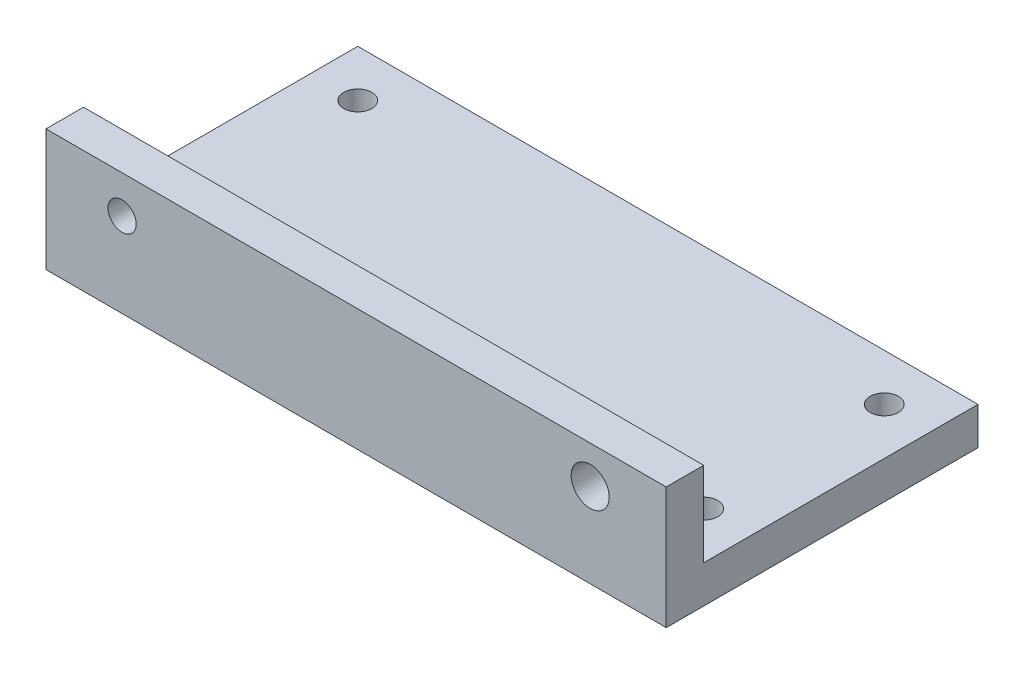
SolidWorks part; units mm, degrees
ref_plane "Front Plane" through (0, 0, 0) normal (0, 0, 1) x (1, 0, 0)
ref_plane "Top Plane" through (0, 0, 0) normal (0, 1, 0) x (1, 0, 0)
ref_plane "Right Plane" through (0, 0, 0) normal (1, 0, 0) x (0, 0, -1)
sketch "Sketch1" plane through (0, 0, 0) normal (0, 1, 0) x (1, 0, 0)
  line L0 (0, 0) -> (0, -20.8457) construction
  line L1 (-33.075, -14.625) -> (33.075, -14.625)
  line L2 (-33.075, -14.625) -> (-33.075, 14.625)
  line L3 (-33.075, 14.625) -> (33.075, 14.625)
  line L4 (33.075, -14.625) -> (33.075, 14.625)
  line L5 (-33.075, -14.625) -> (33.075, 14.625) construction
  line L6 (-33.075, 14.625) -> (33.075, -14.625) construction
  line L7 (0, 0) -> (46.874, 0) construction
  line L8 (-33.075, -14.625) -> (-33.075, -18.625)
  line L9 (-33.075, -18.625) -> (33.075, -18.625)
  line L10 (33.075, -18.625) -> (33.075, -14.625)
  circle A0 centre (-28.075, 9.625) radius 1.5
  circle A1 centre (-28.075, -9.625) radius 1.5
  circle A2 centre (28.075, -9.625) radius 1.5
  circle A3 centre (28.075, 9.625) radius 1.5
  point P0 (0, 0)
  dimension "D1" = 3
  dimension "D2" = 56.15
  dimension "D3" = 19.25
  dimension "D4" = 5
  dimension "D5" = 5
  dimension "D6" = 4
extrude "Boss-Extrude1" add sketch "Sketch1" along normal blind 4 contours L9 L10 L1 L8 | L1 L4 L3 L2 A3 A2 A1 A0 region at (0, 0, 0) region at (0, 0, 16.625)
extrude "Boss-Extrude2" add sketch "Sketch1<3>" along normal blind 9 from surface contours L9 L10 L1 L8 region at (0, 0, 16.625) starting at face at (0, 4, 2)
sketch "Sketch1<3>" plane through (0, 0, 0) normal (0, 1, 0) x (1, 0, 0) same geometry as "Sketch1"
sketch "Sketch2" plane through (0, 0, 18.625) normal (0, 0, 1) x (1, 0, 0)
  line L0 (0, 0) -> (0, 21.1257) construction
  line L1 (33.075, 13) -> (-33.075, 13) construction
  circle A0 centre (-24.96, 9) radius 1.5
  circle A1 centre (24.96, 9) radius 2.0311
  point P6 (0, 0)
  dimension "D1" = 3
  dimension "D2" = 49.92
  dimension "D3" = 4
extrude "Cut-Extrude1" cut sketch "Sketch2" against normal blind 9
